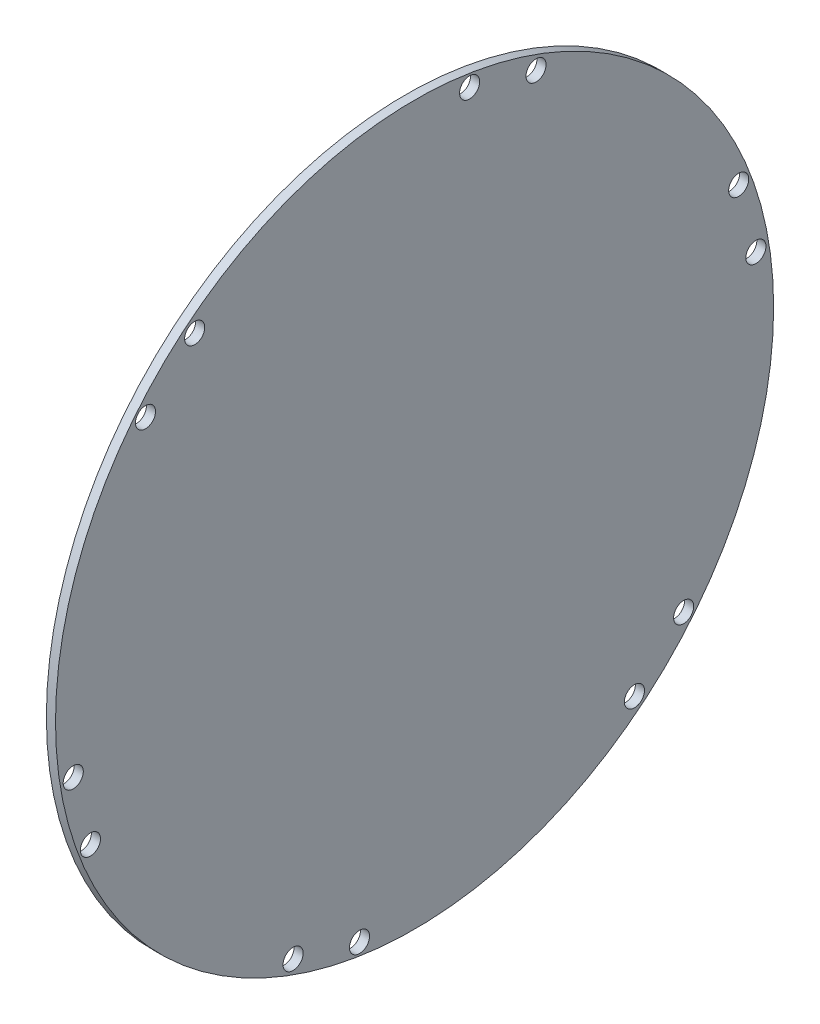
SolidWorks part; units mm, degrees
material "Oak"
ref_plane "Front Plane" through (0, 0, 0) normal (0, 0, 1) x (1, 0, 0)
ref_plane "Top Plane" through (0, 0, 0) normal (0, 1, 0) x (1, 0, 0)
ref_plane "Right Plane" through (0, 0, 0) normal (1, 0, 0) x (0, 0, -1)
sketch "Sketch2" plane through (0, 0, 0) normal (1, 0, 0) x (0, 0, -1)
  circle A0 centre (0, 0) radius 125
  dimension "D1" = 250
extrude "Boss-Extrude1" add sketch "Sketch2" along normal blind 3.18
sketch "Sketch3" plane through (0, 0, 0) normal (-1, 0, 0) x (0, 0, 1)
  circle A5 centre (118.8232, -19.7764) radius 3.5
  circle A12 centre (112.8361, -43.0177) radius 3.5
  circle A13 centre (19.1636, -119.2277) radius 3.5
  circle A14 centre (42.2847, -112.7921) radius 3.5
  circle A15 centre (-76.5385, -93.0157) radius 3.5
  circle A16 centre (-93.6724, -76.2101) radius 3.5
  circle A17 centre (-112.8361, 43.0177) radius 3.5
  circle A18 centre (-118.8232, 19.7764) radius 3.5
  circle A19 centre (-42.2847, 112.7921) radius 3.5
  circle A20 centre (-19.1636, 119.2277) radius 3.5
  circle A21 centre (76.5385, 93.0157) radius 3.5
  circle A22 centre (93.6724, 76.2101) radius 3.5
  dimension "D1" = 7
extrude "Cut-Extrude1" cut sketch "Sketch3" against normal through all
